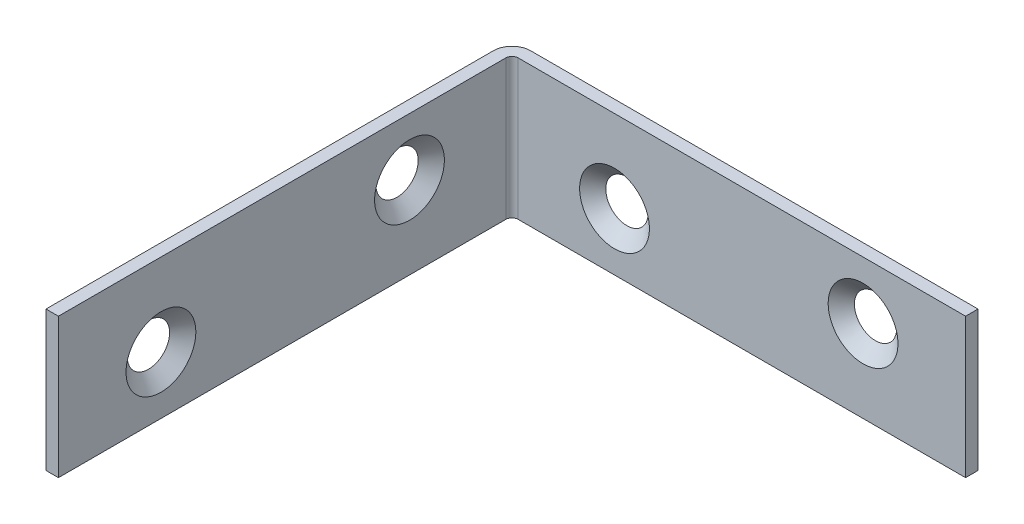
SolidWorks part; units mm, degrees
ref_plane "Front Plane" through (0, 0, 0) normal (0, 0, 1) x (1, 0, 0)
ref_plane "Top Plane" through (0, 0, 0) normal (0, 1, 0) x (1, 0, 0)
ref_plane "Right Plane" through (0, 0, 0) normal (1, 0, 0) x (0, 0, -1)
sketch "Sketch1" plane through (0, 0, 0) normal (0, 1, 0) x (1, 0, 0)
  line L0 (0, -59.9948) -> (0, -2.4003)
  line L1 (2.4003, 0) -> (59.9948, 0)
  line L2 (0, -59.9948) -> (1.6002, -59.9948) construction
  arc A0 (0, -2.4003) -> (2.4003, 0) centre (2.4003, -2.4003) cw
  point P7 (0, 0)
  dimension "D1" = 2.4003
  dimension "Length (A)" = 59.9948
  dimension "Length (B)" = 59.9948
  dimension "Thickness" = 1.6002
sketch "Sketch2" plane through (0, 0, 0) normal (0, 0, 1) x (1, 0, 0)
  line L0 (59.9948, 9.0043) -> (59.9948, -9.0043) construction
  line L1 (1.6002, 0) -> (59.9948, 0) construction
  line L2 (14.7975, -1.5875) -> (46.7975, 1.5875) construction
  circle A0 centre (14.7975, -1.5875) radius 2.2479
  circle A1 centre (46.7975, 1.5875) radius 2.2479
  circle A2 centre (14.7975, -1.5875) radius 4.0005 construction
  point P12 (30.7975, 0)
  dimension "Hole Size" = 4.4958
  dimension "D1" = 8.001
  dimension "Length (C)" = 18.0086
  dimension "Offset" = 3.175
  dimension "On Center" = 32
sketch "Sketch5" plane through (0, 0, 0) normal (0, 1, 0) x (1, 0, 0)
  line L0 (0, 0) -> (50.8394, -50.8394) construction
  line L1 (2.4003, 0) -> (59.9948, 0) construction
  dimension "D1" = 45
ref_axis "Axis1" through (0, 0, 0) along (0.7071, 0, 0.7071)
sketch "Sketch3" plane through (0, 0, 0) normal (0, 1, 0) x (1, 0, 0)
  line L0 (0, -59.9948) -> (0, -2.4003) construction
  line L1 (2.4003, 0) -> (59.9948, 0) construction
  line L2 (0, -59.9948) -> (0, -2.4003)
  line L3 (2.4003, 0) -> (59.9948, 0)
  arc A0 (2.4003, 0) -> (0, -2.4003) centre (2.4003, -2.4003) ccw construction
  arc A1 (2.4003, 0) -> (0, -2.4003) centre (2.4003, -2.4003) ccw
extrude "Extrude-Thin2" add sketch "Sketch3" along normal mid plane 18.0086 thin thin type one direction wall 1.6002
sketch "Sketch4" plane through (0, 0, 0) normal (0, 0, 1) x (1, 0, 0)
  circle A2 centre (46.7975, 1.5875) radius 2.2479 construction
  circle A3 centre (14.7975, -1.5875) radius 2.2479 construction
  circle A4 centre (46.7975, 1.5875) radius 2.2479
  circle A5 centre (14.7975, -1.5875) radius 2.2479
extrude "Cut-Extrude2" cut sketch "Sketch4" along normal through all
chamfer "Chamfer1" distance 2.2479 angle 42 2 edges at (44.5496, 1.5875, 1.6002) (12.5496, -1.5875, 1.6002) first distance on face at (44.5496, 1.5875, 1.6002)
pattern_circular "CirPattern2" count 2 over 180 about axis through (0, 0, 0) along (0.7071, 0, 0.7071) of "Cut-Extrude2", "Chamfer1"
equation "\"D1@Sketch1\"=\"Thickness@Sketch1\"*1.5"
equation "\"D1@Extrude-Thin2\"=\"Length (C)@Sketch2\""
equation "\"D5@Extrude-Thin2\"=\"Thickness@Sketch1\""
equation "\"D1@Chamfer1\"=\"Hole Size@Sketch2\"*.5"
